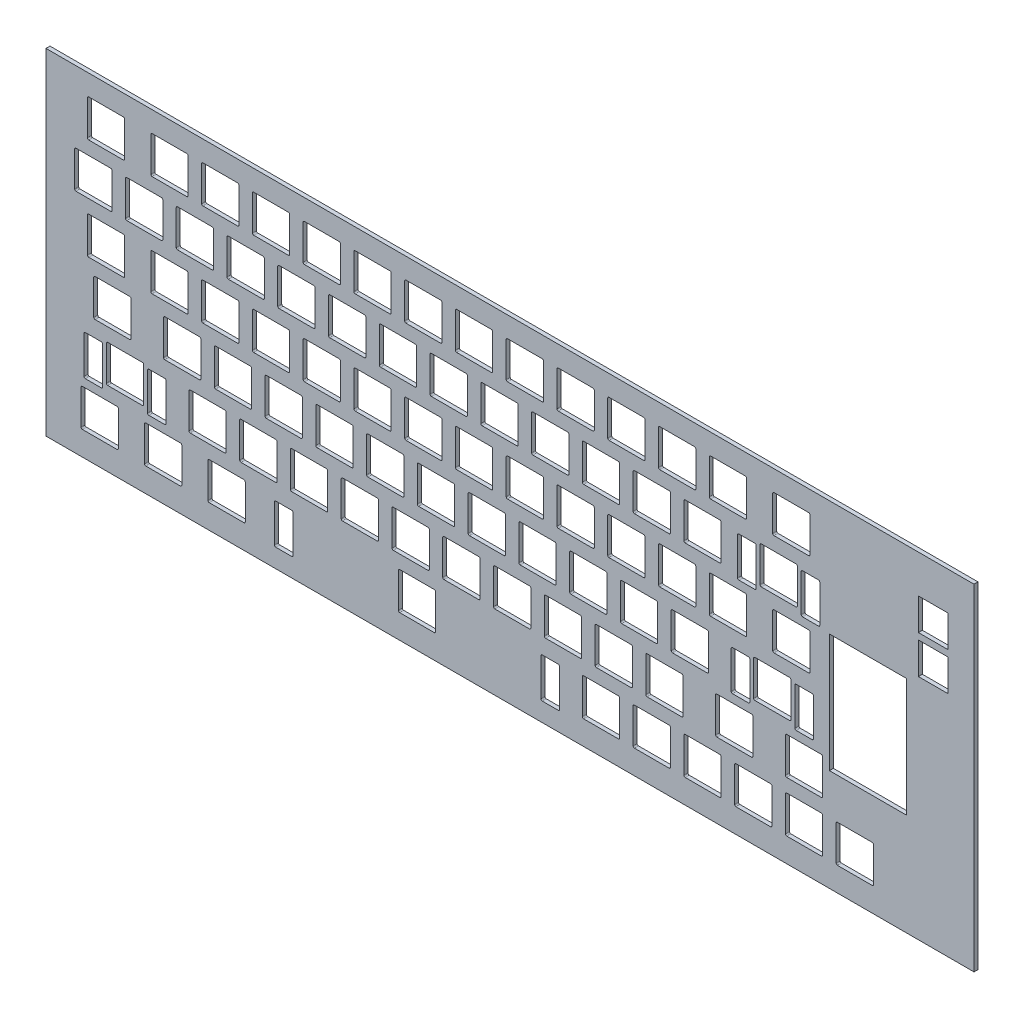
SolidWorks part; units mm, degrees
ref_plane "Front Plane" through (0, 0, 0) normal (0, 0, 1) x (1, 0, 0)
ref_plane "Top Plane" through (0, 0, 0) normal (0, 1, 0) x (1, 0, 0)
ref_plane "Right Plane" through (0, 0, 0) normal (1, 0, 0) x (0, 0, -1)
sketch "Sketch6" plane through (0, 0, 0) normal (0, 0, 1) x (1, 0, 0)
  line L0 (7.7875, -2.525) -> (20.7875, -2.525)
  line L1 (7.7875, -16.525) -> (20.7875, -16.525)
  line L2 (7.2875, -3.025) -> (7.2875, -16.025)
  line L3 (21.2875, -3.025) -> (21.2875, -16.025)
  line L4 (31.6, -2.525) -> (44.6, -2.525)
  line L5 (31.6, -16.525) -> (44.6, -16.525)
  line L6 (31.1, -3.025) -> (31.1, -16.025)
  line L7 (45.1, -3.025) -> (45.1, -16.025)
  line L8 (50.65, -2.525) -> (63.65, -2.525)
  line L9 (50.65, -16.525) -> (63.65, -16.525)
  line L10 (50.15, -3.025) -> (50.15, -16.025)
  line L11 (64.15, -3.025) -> (64.15, -16.025)
  line L12 (69.7, -2.525) -> (82.7, -2.525)
  line L13 (69.7, -16.525) -> (82.7, -16.525)
  line L14 (69.2, -3.025) -> (69.2, -16.025)
  line L15 (83.2, -3.025) -> (83.2, -16.025)
  line L16 (88.75, -2.525) -> (101.75, -2.525)
  line L17 (88.75, -16.525) -> (101.75, -16.525)
  line L18 (88.25, -3.025) -> (88.25, -16.025)
  line L19 (102.25, -3.025) -> (102.25, -16.025)
  line L20 (107.8, -2.525) -> (120.8, -2.525)
  line L21 (107.8, -16.525) -> (120.8, -16.525)
  line L22 (107.3, -3.025) -> (107.3, -16.025)
  line L23 (121.3, -3.025) -> (121.3, -16.025)
  line L24 (126.85, -2.525) -> (139.85, -2.525)
  line L25 (126.85, -16.525) -> (139.85, -16.525)
  line L26 (126.35, -3.025) -> (126.35, -16.025)
  line L27 (140.35, -3.025) -> (140.35, -16.025)
  line L28 (145.9, -2.525) -> (158.9, -2.525)
  line L29 (145.9, -16.525) -> (158.9, -16.525)
  line L30 (145.4, -3.025) -> (145.4, -16.025)
  line L31 (159.4, -3.025) -> (159.4, -16.025)
  line L32 (164.95, -2.525) -> (177.95, -2.525)
  line L33 (164.95, -16.525) -> (177.95, -16.525)
  line L34 (164.45, -3.025) -> (164.45, -16.025)
  line L35 (178.45, -3.025) -> (178.45, -16.025)
  line L36 (184, -2.525) -> (197, -2.525)
  line L37 (184, -16.525) -> (197, -16.525)
  line L38 (183.5, -3.025) -> (183.5, -16.025)
  line L39 (197.5, -3.025) -> (197.5, -16.025)
  line L40 (203.05, -2.525) -> (216.05, -2.525)
  line L41 (203.05, -16.525) -> (216.05, -16.525)
  line L42 (202.55, -3.025) -> (202.55, -16.025)
  line L43 (216.55, -3.025) -> (216.55, -16.025)
  line L44 (222.1, -2.525) -> (235.1, -2.525)
  line L45 (222.1, -16.525) -> (235.1, -16.525)
  line L46 (221.6, -3.025) -> (221.6, -16.025)
  line L47 (235.6, -3.025) -> (235.6, -16.025)
  line L48 (241.15, -2.525) -> (254.15, -2.525)
  line L49 (241.15, -16.525) -> (254.15, -16.525)
  line L50 (240.65, -3.025) -> (240.65, -16.025)
  line L51 (254.65, -3.025) -> (254.65, -16.025)
  line L52 (264.9625, -2.525) -> (277.9625, -2.525)
  line L53 (264.9625, -16.525) -> (277.9625, -16.525)
  line L54 (264.4625, -3.025) -> (264.4625, -16.025)
  line L55 (278.4625, -3.025) -> (278.4625, -16.025)
  line L56 (3.025, -21.575) -> (16.025, -21.575)
  line L57 (3.025, -35.575) -> (16.025, -35.575)
  line L58 (2.525, -22.075) -> (2.525, -35.075)
  line L59 (16.525, -22.075) -> (16.525, -35.075)
  line L60 (22.075, -21.575) -> (35.075, -21.575)
  line L61 (22.075, -35.575) -> (35.075, -35.575)
  line L62 (21.575, -22.075) -> (21.575, -35.075)
  line L63 (35.575, -22.075) -> (35.575, -35.075)
  line L64 (41.125, -21.575) -> (54.125, -21.575)
  line L65 (41.125, -35.575) -> (54.125, -35.575)
  line L66 (40.625, -22.075) -> (40.625, -35.075)
  line L67 (54.625, -22.075) -> (54.625, -35.075)
  line L68 (60.175, -21.575) -> (73.175, -21.575)
  line L69 (60.175, -35.575) -> (73.175, -35.575)
  line L70 (59.675, -22.075) -> (59.675, -35.075)
  line L71 (73.675, -22.075) -> (73.675, -35.075)
  line L72 (79.225, -21.575) -> (92.225, -21.575)
  line L73 (79.225, -35.575) -> (92.225, -35.575)
  line L74 (78.725, -22.075) -> (78.725, -35.075)
  line L75 (92.725, -22.075) -> (92.725, -35.075)
  line L76 (98.275, -21.575) -> (111.275, -21.575)
  line L77 (98.275, -35.575) -> (111.275, -35.575)
  line L78 (97.775, -22.075) -> (97.775, -35.075)
  line L79 (111.775, -22.075) -> (111.775, -35.075)
  line L80 (117.325, -21.575) -> (130.325, -21.575)
  line L81 (117.325, -35.575) -> (130.325, -35.575)
  line L82 (116.825, -22.075) -> (116.825, -35.075)
  line L83 (130.825, -22.075) -> (130.825, -35.075)
  line L84 (136.375, -21.575) -> (149.375, -21.575)
  line L85 (136.375, -35.575) -> (149.375, -35.575)
  line L86 (135.875, -22.075) -> (135.875, -35.075)
  line L87 (149.875, -22.075) -> (149.875, -35.075)
  line L88 (155.425, -21.575) -> (168.425, -21.575)
  line L89 (155.425, -35.575) -> (168.425, -35.575)
  line L90 (154.925, -22.075) -> (154.925, -35.075)
  line L91 (168.925, -22.075) -> (168.925, -35.075)
  line L92 (174.475, -21.575) -> (187.475, -21.575)
  line L93 (174.475, -35.575) -> (187.475, -35.575)
  line L94 (173.975, -22.075) -> (173.975, -35.075)
  line L95 (187.975, -22.075) -> (187.975, -35.075)
  line L96 (193.525, -21.575) -> (206.525, -21.575)
  line L97 (193.525, -35.575) -> (206.525, -35.575)
  line L98 (193.025, -22.075) -> (193.025, -35.075)
  line L99 (207.025, -22.075) -> (207.025, -35.075)
  line L100 (212.575, -21.575) -> (225.575, -21.575)
  line L101 (212.575, -35.575) -> (225.575, -35.575)
  line L102 (212.075, -22.075) -> (212.075, -35.075)
  line L103 (226.075, -22.075) -> (226.075, -35.075)
  line L104 (231.625, -21.575) -> (244.625, -21.575)
  line L105 (231.625, -35.575) -> (244.625, -35.575)
  line L106 (231.125, -22.075) -> (231.125, -35.075)
  line L107 (245.125, -22.075) -> (245.125, -35.075)
  line L108 (260.2, -21.575) -> (273.2, -21.575)
  line L109 (260.2, -35.575) -> (273.2, -35.575)
  line L110 (259.7, -22.075) -> (259.7, -35.075)
  line L111 (273.7, -22.075) -> (273.7, -35.075)
  line L112 (251.762, -22.575) -> (257.762, -22.575)
  line L113 (251.762, -37.575) -> (257.762, -37.575)
  line L114 (251.262, -23.075) -> (251.262, -37.075)
  line L115 (258.262, -23.075) -> (258.262, -37.075)
  line L116 (275.638, -22.575) -> (281.638, -22.575)
  line L117 (275.638, -37.575) -> (281.638, -37.575)
  line L118 (275.138, -23.075) -> (275.138, -37.075)
  line L119 (282.138, -23.075) -> (282.138, -37.075)
  line L120 (7.7875, -40.625) -> (20.7875, -40.625)
  line L121 (7.7875, -54.625) -> (20.7875, -54.625)
  line L122 (7.2875, -41.125) -> (7.2875, -54.125)
  line L123 (21.2875, -41.125) -> (21.2875, -54.125)
  line L124 (31.6, -40.625) -> (44.6, -40.625)
  line L125 (31.6, -54.625) -> (44.6, -54.625)
  line L126 (31.1, -41.125) -> (31.1, -54.125)
  line L127 (45.1, -41.125) -> (45.1, -54.125)
  line L128 (50.65, -40.625) -> (63.65, -40.625)
  line L129 (50.65, -54.625) -> (63.65, -54.625)
  line L130 (50.15, -41.125) -> (50.15, -54.125)
  line L131 (64.15, -41.125) -> (64.15, -54.125)
  line L132 (69.7, -40.625) -> (82.7, -40.625)
  line L133 (69.7, -54.625) -> (82.7, -54.625)
  line L134 (69.2, -41.125) -> (69.2, -54.125)
  line L135 (83.2, -41.125) -> (83.2, -54.125)
  line L136 (88.75, -40.625) -> (101.75, -40.625)
  line L137 (88.75, -54.625) -> (101.75, -54.625)
  line L138 (88.25, -41.125) -> (88.25, -54.125)
  line L139 (102.25, -41.125) -> (102.25, -54.125)
  line L140 (107.8, -40.625) -> (120.8, -40.625)
  line L141 (107.8, -54.625) -> (120.8, -54.625)
  line L142 (107.3, -41.125) -> (107.3, -54.125)
  line L143 (121.3, -41.125) -> (121.3, -54.125)
  line L144 (126.85, -40.625) -> (139.85, -40.625)
  line L145 (126.85, -54.625) -> (139.85, -54.625)
  line L146 (126.35, -41.125) -> (126.35, -54.125)
  line L147 (140.35, -41.125) -> (140.35, -54.125)
  line L148 (145.9, -40.625) -> (158.9, -40.625)
  line L149 (145.9, -54.625) -> (158.9, -54.625)
  line L150 (145.4, -41.125) -> (145.4, -54.125)
  line L151 (159.4, -41.125) -> (159.4, -54.125)
  line L152 (164.95, -40.625) -> (177.95, -40.625)
  line L153 (164.95, -54.625) -> (177.95, -54.625)
  line L154 (164.45, -41.125) -> (164.45, -54.125)
  line L155 (178.45, -41.125) -> (178.45, -54.125)
  line L156 (184, -40.625) -> (197, -40.625)
  line L157 (184, -54.625) -> (197, -54.625)
  line L158 (183.5, -41.125) -> (183.5, -54.125)
  line L159 (197.5, -41.125) -> (197.5, -54.125)
  line L160 (203.05, -40.625) -> (216.05, -40.625)
  line L161 (203.05, -54.625) -> (216.05, -54.625)
  line L162 (202.55, -41.125) -> (202.55, -54.125)
  line L163 (216.55, -41.125) -> (216.55, -54.125)
  line L164 (222.1, -40.625) -> (235.1, -40.625)
  line L165 (222.1, -54.625) -> (235.1, -54.625)
  line L166 (221.6, -41.125) -> (221.6, -54.125)
  line L167 (235.6, -41.125) -> (235.6, -54.125)
  line L168 (241.15, -40.625) -> (254.15, -40.625)
  line L169 (241.15, -54.625) -> (254.15, -54.625)
  line L170 (240.65, -41.125) -> (240.65, -54.125)
  line L171 (254.65, -41.125) -> (254.65, -54.125)
  line L172 (264.9625, -40.625) -> (277.9625, -40.625)
  line L173 (264.9625, -54.625) -> (277.9625, -54.625)
  line L174 (264.4625, -41.125) -> (264.4625, -54.125)
  line L175 (278.4625, -41.125) -> (278.4625, -54.125)
  line L176 (10.1687, -59.675) -> (23.1687, -59.675)
  line L177 (10.1687, -73.675) -> (23.1687, -73.675)
  line L178 (9.6688, -60.175) -> (9.6688, -73.175)
  line L179 (23.6687, -60.175) -> (23.6687, -73.175)
  line L180 (36.3625, -59.675) -> (49.3625, -59.675)
  line L181 (36.3625, -73.675) -> (49.3625, -73.675)
  line L182 (35.8625, -60.175) -> (35.8625, -73.175)
  line L183 (49.8625, -60.175) -> (49.8625, -73.175)
  line L184 (55.4125, -59.675) -> (68.4125, -59.675)
  line L185 (55.4125, -73.675) -> (68.4125, -73.675)
  line L186 (54.9125, -60.175) -> (54.9125, -73.175)
  line L187 (68.9125, -60.175) -> (68.9125, -73.175)
  line L188 (74.4625, -59.675) -> (87.4625, -59.675)
  line L189 (74.4625, -73.675) -> (87.4625, -73.675)
  line L190 (73.9625, -60.175) -> (73.9625, -73.175)
  line L191 (87.9625, -60.175) -> (87.9625, -73.175)
  line L192 (93.5125, -59.675) -> (106.5125, -59.675)
  line L193 (93.5125, -73.675) -> (106.5125, -73.675)
  line L194 (93.0125, -60.175) -> (93.0125, -73.175)
  line L195 (107.0125, -60.175) -> (107.0125, -73.175)
  line L196 (112.5625, -59.675) -> (125.5625, -59.675)
  line L197 (112.5625, -73.675) -> (125.5625, -73.675)
  line L198 (112.0625, -60.175) -> (112.0625, -73.175)
  line L199 (126.0625, -60.175) -> (126.0625, -73.175)
  line L200 (131.6125, -59.675) -> (144.6125, -59.675)
  line L201 (131.6125, -73.675) -> (144.6125, -73.675)
  line L202 (131.1125, -60.175) -> (131.1125, -73.175)
  line L203 (145.1125, -60.175) -> (145.1125, -73.175)
  line L204 (150.6625, -59.675) -> (163.6625, -59.675)
  line L205 (150.6625, -73.675) -> (163.6625, -73.675)
  line L206 (150.1625, -60.175) -> (150.1625, -73.175)
  line L207 (164.1625, -60.175) -> (164.1625, -73.175)
  line L208 (169.7125, -59.675) -> (182.7125, -59.675)
  line L209 (169.7125, -73.675) -> (182.7125, -73.675)
  line L210 (169.2125, -60.175) -> (169.2125, -73.175)
  line L211 (183.2125, -60.175) -> (183.2125, -73.175)
  line L212 (188.7625, -59.675) -> (201.7625, -59.675)
  line L213 (188.7625, -73.675) -> (201.7625, -73.675)
  line L214 (188.2625, -60.175) -> (188.2625, -73.175)
  line L215 (202.2625, -60.175) -> (202.2625, -73.175)
  line L216 (207.8125, -59.675) -> (220.8125, -59.675)
  line L217 (207.8125, -73.675) -> (220.8125, -73.675)
  line L218 (207.3125, -60.175) -> (207.3125, -73.175)
  line L219 (221.3125, -60.175) -> (221.3125, -73.175)
  line L220 (226.8625, -59.675) -> (239.8625, -59.675)
  line L221 (226.8625, -73.675) -> (239.8625, -73.675)
  line L222 (226.3625, -60.175) -> (226.3625, -73.175)
  line L223 (240.3625, -60.175) -> (240.3625, -73.175)
  line L224 (257.8188, -59.675) -> (270.8188, -59.675)
  line L225 (257.8188, -73.675) -> (270.8188, -73.675)
  line L226 (257.3188, -60.175) -> (257.3188, -73.175)
  line L227 (271.3188, -60.175) -> (271.3188, -73.175)
  line L228 (249.3808, -60.675) -> (255.3807, -60.675)
  line L229 (249.3808, -75.675) -> (255.3807, -75.675)
  line L230 (248.8808, -61.175) -> (248.8808, -75.175)
  line L231 (255.8807, -61.175) -> (255.8807, -75.175)
  line L232 (273.2568, -60.675) -> (279.2568, -60.675)
  line L233 (273.2568, -75.675) -> (279.2568, -75.675)
  line L234 (272.7568, -61.175) -> (272.7568, -75.175)
  line L235 (279.7568, -61.175) -> (279.7568, -75.175)
  line L236 (14.9313, -78.725) -> (27.9312, -78.725)
  line L237 (14.9313, -92.725) -> (27.9312, -92.725)
  line L238 (14.4313, -79.225) -> (14.4313, -92.225)
  line L239 (28.4312, -79.225) -> (28.4312, -92.225)
  line L240 (6.4932, -79.725) -> (12.4932, -79.725)
  line L241 (6.4932, -94.725) -> (12.4932, -94.725)
  line L242 (5.9932, -80.225) -> (5.9932, -94.225)
  line L243 (12.9932, -80.225) -> (12.9932, -94.225)
  line L244 (30.3693, -79.725) -> (36.3693, -79.725)
  line L245 (30.3693, -94.725) -> (36.3693, -94.725)
  line L246 (29.8693, -80.225) -> (29.8693, -94.225)
  line L247 (36.8693, -80.225) -> (36.8693, -94.225)
  line L248 (45.8875, -78.725) -> (58.8875, -78.725)
  line L249 (45.8875, -92.725) -> (58.8875, -92.725)
  line L250 (45.3875, -79.225) -> (45.3875, -92.225)
  line L251 (59.3875, -79.225) -> (59.3875, -92.225)
  line L252 (64.9375, -78.725) -> (77.9375, -78.725)
  line L253 (64.9375, -92.725) -> (77.9375, -92.725)
  line L254 (64.4375, -79.225) -> (64.4375, -92.225)
  line L255 (78.4375, -79.225) -> (78.4375, -92.225)
  line L256 (83.9875, -78.725) -> (96.9875, -78.725)
  line L257 (83.9875, -92.725) -> (96.9875, -92.725)
  line L258 (83.4875, -79.225) -> (83.4875, -92.225)
  line L259 (97.4875, -79.225) -> (97.4875, -92.225)
  line L260 (103.0375, -78.725) -> (116.0375, -78.725)
  line L261 (103.0375, -92.725) -> (116.0375, -92.725)
  line L262 (102.5375, -79.225) -> (102.5375, -92.225)
  line L263 (116.5375, -79.225) -> (116.5375, -92.225)
  line L264 (122.0875, -78.725) -> (135.0875, -78.725)
  line L265 (122.0875, -92.725) -> (135.0875, -92.725)
  line L266 (121.5875, -79.225) -> (121.5875, -92.225)
  line L267 (135.5875, -79.225) -> (135.5875, -92.225)
  line L268 (141.1375, -78.725) -> (154.1375, -78.725)
  line L269 (141.1375, -92.725) -> (154.1375, -92.725)
  line L270 (140.6375, -79.225) -> (140.6375, -92.225)
  line L271 (154.6375, -79.225) -> (154.6375, -92.225)
  line L272 (160.1875, -78.725) -> (173.1875, -78.725)
  line L273 (160.1875, -92.725) -> (173.1875, -92.725)
  line L274 (159.6875, -79.225) -> (159.6875, -92.225)
  line L275 (173.6875, -79.225) -> (173.6875, -92.225)
  line L276 (179.2375, -78.725) -> (192.2375, -78.725)
  line L277 (179.2375, -92.725) -> (192.2375, -92.725)
  line L278 (178.7375, -79.225) -> (178.7375, -92.225)
  line L279 (192.7375, -79.225) -> (192.7375, -92.225)
  line L280 (198.2875, -78.725) -> (211.2875, -78.725)
  line L281 (198.2875, -92.725) -> (211.2875, -92.725)
  line L282 (197.7875, -79.225) -> (197.7875, -92.225)
  line L283 (211.7875, -79.225) -> (211.7875, -92.225)
  line L284 (217.3375, -78.725) -> (230.3375, -78.725)
  line L285 (217.3375, -92.725) -> (230.3375, -92.725)
  line L286 (216.8375, -79.225) -> (216.8375, -92.225)
  line L287 (230.8375, -79.225) -> (230.8375, -92.225)
  line L288 (243.5312, -78.725) -> (256.5312, -78.725)
  line L289 (243.5312, -92.725) -> (256.5312, -92.725)
  line L290 (243.0312, -79.225) -> (243.0312, -92.225)
  line L291 (257.0312, -79.225) -> (257.0312, -92.225)
  line L292 (269.725, -78.725) -> (282.725, -78.725)
  line L293 (269.725, -92.725) -> (282.725, -92.725)
  line L294 (269.225, -79.225) -> (269.225, -92.225)
  line L295 (283.225, -79.225) -> (283.225, -92.225)
  line L296 (5.4063, -97.775) -> (18.4062, -97.775)
  line L297 (5.4063, -111.775) -> (18.4062, -111.775)
  line L298 (4.9062, -98.275) -> (4.9062, -111.275)
  line L299 (18.9062, -98.275) -> (18.9062, -111.275)
  line L300 (29.2188, -97.775) -> (42.2188, -97.775)
  line L301 (29.2188, -111.775) -> (42.2188, -111.775)
  line L302 (28.7188, -98.275) -> (28.7188, -111.275)
  line L303 (42.7188, -98.275) -> (42.7188, -111.275)
  line L304 (53.0312, -97.775) -> (66.0312, -97.775)
  line L305 (53.0312, -111.775) -> (66.0312, -111.775)
  line L306 (52.5312, -98.275) -> (52.5312, -111.275)
  line L307 (66.5312, -98.275) -> (66.5312, -111.275)
  line L308 (124.4688, -97.775) -> (137.4688, -97.775)
  line L309 (124.4688, -111.775) -> (137.4688, -111.775)
  line L310 (123.9688, -98.275) -> (123.9688, -111.275)
  line L311 (137.9688, -98.275) -> (137.9688, -111.275)
  line L312 (77.9688, -98.775) -> (83.9688, -98.775)
  line L313 (77.9688, -113.775) -> (83.9688, -113.775)
  line L314 (77.4688, -99.275) -> (77.4688, -113.275)
  line L315 (84.4688, -99.275) -> (84.4688, -113.275)
  line L316 (177.9688, -98.775) -> (183.9688, -98.775)
  line L317 (177.9688, -113.775) -> (183.9688, -113.775)
  line L318 (177.4688, -99.275) -> (177.4688, -113.275)
  line L319 (184.4688, -99.275) -> (184.4688, -113.275)
  line L320 (193.525, -97.775) -> (206.525, -97.775)
  line L321 (193.525, -111.775) -> (206.525, -111.775)
  line L322 (193.025, -98.275) -> (193.025, -111.275)
  line L323 (207.025, -98.275) -> (207.025, -111.275)
  line L324 (212.575, -97.775) -> (225.575, -97.775)
  line L325 (212.575, -111.775) -> (225.575, -111.775)
  line L326 (212.075, -98.275) -> (212.075, -111.275)
  line L327 (226.075, -98.275) -> (226.075, -111.275)
  line L328 (231.625, -97.775) -> (244.625, -97.775)
  line L329 (231.625, -111.775) -> (244.625, -111.775)
  line L330 (231.125, -98.275) -> (231.125, -111.275)
  line L331 (245.125, -98.275) -> (245.125, -111.275)
  line L332 (250.675, -97.775) -> (263.675, -97.775)
  line L333 (250.675, -111.775) -> (263.675, -111.775)
  line L334 (250.175, -98.275) -> (250.175, -111.275)
  line L335 (264.175, -98.275) -> (264.175, -111.275)
  line L336 (269.725, -97.775) -> (282.725, -97.775)
  line L337 (269.725, -111.775) -> (282.725, -111.775)
  line L338 (269.225, -98.275) -> (269.225, -111.275)
  line L339 (283.225, -98.275) -> (283.225, -111.275)
  line L340 (288.775, -97.775) -> (301.775, -97.775)
  line L341 (288.775, -111.775) -> (301.775, -111.775)
  line L342 (288.275, -98.275) -> (288.275, -111.275)
  line L343 (302.275, -98.275) -> (302.275, -111.275)
  line L346 (0, -114.3) -> (0, 0)
  line L348 (0, 0) -> (340, 0)
  line L350 (0, -114.3) -> (340, -114.3)
  line L351 (340, 0) -> (340, -114.3)
  line L352 (285.74, -38.08) -> (314.74, -38.08)
  line L353 (285.74, -38.08) -> (285.74, -82.5)
  line L354 (285.74, -82.5) -> (314.74, -82.5)
  line L355 (314.74, -38.08) -> (314.74, -82.5)
  line L356 (319.14, -9.03) -> (330.19, -9.03)
  line L357 (319.14, -9.03) -> (319.14, -20.93)
  line L358 (319.14, -20.93) -> (330.19, -20.93)
  line L359 (330.19, -9.03) -> (330.19, -20.93)
  line L360 (319.14, -23.33) -> (330.19, -23.33)
  line L361 (319.14, -23.33) -> (319.14, -35.23)
  line L362 (319.14, -35.23) -> (330.19, -35.23)
  line L363 (330.19, -23.33) -> (330.19, -35.23)
  arc A0 (7.7875, -2.525) -> (7.2875, -3.025) centre (7.7875, -3.025) ccw
  arc A1 (21.2875, -3.025) -> (20.7875, -2.525) centre (20.7875, -3.025) ccw
  arc A2 (7.2875, -16.025) -> (7.7875, -16.525) centre (7.7875, -16.025) ccw
  arc A3 (20.7875, -16.525) -> (21.2875, -16.025) centre (20.7875, -16.025) ccw
  arc A4 (31.6, -2.525) -> (31.1, -3.025) centre (31.6, -3.025) ccw
  arc A5 (45.1, -3.025) -> (44.6, -2.525) centre (44.6, -3.025) ccw
  arc A6 (31.1, -16.025) -> (31.6, -16.525) centre (31.6, -16.025) ccw
  arc A7 (44.6, -16.525) -> (45.1, -16.025) centre (44.6, -16.025) ccw
  arc A8 (50.65, -2.525) -> (50.15, -3.025) centre (50.65, -3.025) ccw
  arc A9 (64.15, -3.025) -> (63.65, -2.525) centre (63.65, -3.025) ccw
  arc A10 (50.15, -16.025) -> (50.65, -16.525) centre (50.65, -16.025) ccw
  arc A11 (63.65, -16.525) -> (64.15, -16.025) centre (63.65, -16.025) ccw
  arc A12 (69.7, -2.525) -> (69.2, -3.025) centre (69.7, -3.025) ccw
  arc A13 (83.2, -3.025) -> (82.7, -2.525) centre (82.7, -3.025) ccw
  arc A14 (69.2, -16.025) -> (69.7, -16.525) centre (69.7, -16.025) ccw
  arc A15 (82.7, -16.525) -> (83.2, -16.025) centre (82.7, -16.025) ccw
  arc A16 (88.75, -2.525) -> (88.25, -3.025) centre (88.75, -3.025) ccw
  arc A17 (102.25, -3.025) -> (101.75, -2.525) centre (101.75, -3.025) ccw
  arc A18 (88.25, -16.025) -> (88.75, -16.525) centre (88.75, -16.025) ccw
  arc A19 (101.75, -16.525) -> (102.25, -16.025) centre (101.75, -16.025) ccw
  arc A20 (107.8, -2.525) -> (107.3, -3.025) centre (107.8, -3.025) ccw
  arc A21 (121.3, -3.025) -> (120.8, -2.525) centre (120.8, -3.025) ccw
  arc A22 (107.3, -16.025) -> (107.8, -16.525) centre (107.8, -16.025) ccw
  arc A23 (120.8, -16.525) -> (121.3, -16.025) centre (120.8, -16.025) ccw
  arc A24 (126.85, -2.525) -> (126.35, -3.025) centre (126.85, -3.025) ccw
  arc A25 (140.35, -3.025) -> (139.85, -2.525) centre (139.85, -3.025) ccw
  arc A26 (126.35, -16.025) -> (126.85, -16.525) centre (126.85, -16.025) ccw
  arc A27 (139.85, -16.525) -> (140.35, -16.025) centre (139.85, -16.025) ccw
  arc A28 (145.9, -2.525) -> (145.4, -3.025) centre (145.9, -3.025) ccw
  arc A29 (159.4, -3.025) -> (158.9, -2.525) centre (158.9, -3.025) ccw
  arc A30 (145.4, -16.025) -> (145.9, -16.525) centre (145.9, -16.025) ccw
  arc A31 (158.9, -16.525) -> (159.4, -16.025) centre (158.9, -16.025) ccw
  arc A32 (164.95, -2.525) -> (164.45, -3.025) centre (164.95, -3.025) ccw
  arc A33 (178.45, -3.025) -> (177.95, -2.525) centre (177.95, -3.025) ccw
  arc A34 (164.45, -16.025) -> (164.95, -16.525) centre (164.95, -16.025) ccw
  arc A35 (177.95, -16.525) -> (178.45, -16.025) centre (177.95, -16.025) ccw
  arc A36 (184, -2.525) -> (183.5, -3.025) centre (184, -3.025) ccw
  arc A37 (197.5, -3.025) -> (197, -2.525) centre (197, -3.025) ccw
  arc A38 (183.5, -16.025) -> (184, -16.525) centre (184, -16.025) ccw
  arc A39 (197, -16.525) -> (197.5, -16.025) centre (197, -16.025) ccw
  arc A40 (203.05, -2.525) -> (202.55, -3.025) centre (203.05, -3.025) ccw
  arc A41 (216.55, -3.025) -> (216.05, -2.525) centre (216.05, -3.025) ccw
  arc A42 (202.55, -16.025) -> (203.05, -16.525) centre (203.05, -16.025) ccw
  arc A43 (216.05, -16.525) -> (216.55, -16.025) centre (216.05, -16.025) ccw
  arc A44 (222.1, -2.525) -> (221.6, -3.025) centre (222.1, -3.025) ccw
  arc A45 (235.6, -3.025) -> (235.1, -2.525) centre (235.1, -3.025) ccw
  arc A46 (221.6, -16.025) -> (222.1, -16.525) centre (222.1, -16.025) ccw
  arc A47 (235.1, -16.525) -> (235.6, -16.025) centre (235.1, -16.025) ccw
  arc A48 (241.15, -2.525) -> (240.65, -3.025) centre (241.15, -3.025) ccw
  arc A49 (254.65, -3.025) -> (254.15, -2.525) centre (254.15, -3.025) ccw
  arc A50 (240.65, -16.025) -> (241.15, -16.525) centre (241.15, -16.025) ccw
  arc A51 (254.15, -16.525) -> (254.65, -16.025) centre (254.15, -16.025) ccw
  arc A52 (264.9625, -2.525) -> (264.4625, -3.025) centre (264.9625, -3.025) ccw
  arc A53 (278.4625, -3.025) -> (277.9625, -2.525) centre (277.9625, -3.025) ccw
  arc A54 (264.4625, -16.025) -> (264.9625, -16.525) centre (264.9625, -16.025) ccw
  arc A55 (277.9625, -16.525) -> (278.4625, -16.025) centre (277.9625, -16.025) ccw
  arc A56 (3.025, -21.575) -> (2.525, -22.075) centre (3.025, -22.075) ccw
  arc A57 (16.525, -22.075) -> (16.025, -21.575) centre (16.025, -22.075) ccw
  arc A58 (2.525, -35.075) -> (3.025, -35.575) centre (3.025, -35.075) ccw
  arc A59 (16.025, -35.575) -> (16.525, -35.075) centre (16.025, -35.075) ccw
  arc A60 (22.075, -21.575) -> (21.575, -22.075) centre (22.075, -22.075) ccw
  arc A61 (35.575, -22.075) -> (35.075, -21.575) centre (35.075, -22.075) ccw
  arc A62 (21.575, -35.075) -> (22.075, -35.575) centre (22.075, -35.075) ccw
  arc A63 (35.075, -35.575) -> (35.575, -35.075) centre (35.075, -35.075) ccw
  arc A64 (41.125, -21.575) -> (40.625, -22.075) centre (41.125, -22.075) ccw
  arc A65 (54.625, -22.075) -> (54.125, -21.575) centre (54.125, -22.075) ccw
  arc A66 (40.625, -35.075) -> (41.125, -35.575) centre (41.125, -35.075) ccw
  arc A67 (54.125, -35.575) -> (54.625, -35.075) centre (54.125, -35.075) ccw
  arc A68 (60.175, -21.575) -> (59.675, -22.075) centre (60.175, -22.075) ccw
  arc A69 (73.675, -22.075) -> (73.175, -21.575) centre (73.175, -22.075) ccw
  arc A70 (59.675, -35.075) -> (60.175, -35.575) centre (60.175, -35.075) ccw
  arc A71 (73.175, -35.575) -> (73.675, -35.075) centre (73.175, -35.075) ccw
  arc A72 (79.225, -21.575) -> (78.725, -22.075) centre (79.225, -22.075) ccw
  arc A73 (92.725, -22.075) -> (92.225, -21.575) centre (92.225, -22.075) ccw
  arc A74 (78.725, -35.075) -> (79.225, -35.575) centre (79.225, -35.075) ccw
  arc A75 (92.225, -35.575) -> (92.725, -35.075) centre (92.225, -35.075) ccw
  arc A76 (98.275, -21.575) -> (97.775, -22.075) centre (98.275, -22.075) ccw
  arc A77 (111.775, -22.075) -> (111.275, -21.575) centre (111.275, -22.075) ccw
  arc A78 (97.775, -35.075) -> (98.275, -35.575) centre (98.275, -35.075) ccw
  arc A79 (111.275, -35.575) -> (111.775, -35.075) centre (111.275, -35.075) ccw
  arc A80 (117.325, -21.575) -> (116.825, -22.075) centre (117.325, -22.075) ccw
  arc A81 (130.825, -22.075) -> (130.325, -21.575) centre (130.325, -22.075) ccw
  arc A82 (116.825, -35.075) -> (117.325, -35.575) centre (117.325, -35.075) ccw
  arc A83 (130.325, -35.575) -> (130.825, -35.075) centre (130.325, -35.075) ccw
  arc A84 (136.375, -21.575) -> (135.875, -22.075) centre (136.375, -22.075) ccw
  arc A85 (149.875, -22.075) -> (149.375, -21.575) centre (149.375, -22.075) ccw
  arc A86 (135.875, -35.075) -> (136.375, -35.575) centre (136.375, -35.075) ccw
  arc A87 (149.375, -35.575) -> (149.875, -35.075) centre (149.375, -35.075) ccw
  arc A88 (155.425, -21.575) -> (154.925, -22.075) centre (155.425, -22.075) ccw
  arc A89 (168.925, -22.075) -> (168.425, -21.575) centre (168.425, -22.075) ccw
  arc A90 (154.925, -35.075) -> (155.425, -35.575) centre (155.425, -35.075) ccw
  arc A91 (168.425, -35.575) -> (168.925, -35.075) centre (168.425, -35.075) ccw
  arc A92 (174.475, -21.575) -> (173.975, -22.075) centre (174.475, -22.075) ccw
  arc A93 (187.975, -22.075) -> (187.475, -21.575) centre (187.475, -22.075) ccw
  arc A94 (173.975, -35.075) -> (174.475, -35.575) centre (174.475, -35.075) ccw
  arc A95 (187.475, -35.575) -> (187.975, -35.075) centre (187.475, -35.075) ccw
  arc A96 (193.525, -21.575) -> (193.025, -22.075) centre (193.525, -22.075) ccw
  arc A97 (207.025, -22.075) -> (206.525, -21.575) centre (206.525, -22.075) ccw
  arc A98 (193.025, -35.075) -> (193.525, -35.575) centre (193.525, -35.075) ccw
  arc A99 (206.525, -35.575) -> (207.025, -35.075) centre (206.525, -35.075) ccw
  arc A100 (212.575, -21.575) -> (212.075, -22.075) centre (212.575, -22.075) ccw
  arc A101 (226.075, -22.075) -> (225.575, -21.575) centre (225.575, -22.075) ccw
  arc A102 (212.075, -35.075) -> (212.575, -35.575) centre (212.575, -35.075) ccw
  arc A103 (225.575, -35.575) -> (226.075, -35.075) centre (225.575, -35.075) ccw
  arc A104 (231.625, -21.575) -> (231.125, -22.075) centre (231.625, -22.075) ccw
  arc A105 (245.125, -22.075) -> (244.625, -21.575) centre (244.625, -22.075) ccw
  arc A106 (231.125, -35.075) -> (231.625, -35.575) centre (231.625, -35.075) ccw
  arc A107 (244.625, -35.575) -> (245.125, -35.075) centre (244.625, -35.075) ccw
  arc A108 (260.2, -21.575) -> (259.7, -22.075) centre (260.2, -22.075) ccw
  arc A109 (273.7, -22.075) -> (273.2, -21.575) centre (273.2, -22.075) ccw
  arc A110 (259.7, -35.075) -> (260.2, -35.575) centre (260.2, -35.075) ccw
  arc A111 (273.2, -35.575) -> (273.7, -35.075) centre (273.2, -35.075) ccw
  arc A112 (251.762, -22.575) -> (251.262, -23.075) centre (251.762, -23.075) ccw
  arc A113 (258.262, -23.075) -> (257.762, -22.575) centre (257.762, -23.075) ccw
  arc A114 (251.262, -37.075) -> (251.762, -37.575) centre (251.762, -37.075) ccw
  arc A115 (257.762, -37.575) -> (258.262, -37.075) centre (257.762, -37.075) ccw
  arc A116 (275.638, -22.575) -> (275.138, -23.075) centre (275.638, -23.075) ccw
  arc A117 (282.138, -23.075) -> (281.638, -22.575) centre (281.638, -23.075) ccw
  arc A118 (275.138, -37.075) -> (275.638, -37.575) centre (275.638, -37.075) ccw
  arc A119 (281.638, -37.575) -> (282.138, -37.075) centre (281.638, -37.075) ccw
  arc A120 (7.7875, -40.625) -> (7.2875, -41.125) centre (7.7875, -41.125) ccw
  arc A121 (21.2875, -41.125) -> (20.7875, -40.625) centre (20.7875, -41.125) ccw
  arc A122 (7.2875, -54.125) -> (7.7875, -54.625) centre (7.7875, -54.125) ccw
  arc A123 (20.7875, -54.625) -> (21.2875, -54.125) centre (20.7875, -54.125) ccw
  arc A124 (31.6, -40.625) -> (31.1, -41.125) centre (31.6, -41.125) ccw
  arc A125 (45.1, -41.125) -> (44.6, -40.625) centre (44.6, -41.125) ccw
  arc A126 (31.1, -54.125) -> (31.6, -54.625) centre (31.6, -54.125) ccw
  arc A127 (44.6, -54.625) -> (45.1, -54.125) centre (44.6, -54.125) ccw
  arc A128 (50.65, -40.625) -> (50.15, -41.125) centre (50.65, -41.125) ccw
  arc A129 (64.15, -41.125) -> (63.65, -40.625) centre (63.65, -41.125) ccw
  arc A130 (50.15, -54.125) -> (50.65, -54.625) centre (50.65, -54.125) ccw
  arc A131 (63.65, -54.625) -> (64.15, -54.125) centre (63.65, -54.125) ccw
  arc A132 (69.7, -40.625) -> (69.2, -41.125) centre (69.7, -41.125) ccw
  arc A133 (83.2, -41.125) -> (82.7, -40.625) centre (82.7, -41.125) ccw
  arc A134 (69.2, -54.125) -> (69.7, -54.625) centre (69.7, -54.125) ccw
  arc A135 (82.7, -54.625) -> (83.2, -54.125) centre (82.7, -54.125) ccw
  arc A136 (88.75, -40.625) -> (88.25, -41.125) centre (88.75, -41.125) ccw
  arc A137 (102.25, -41.125) -> (101.75, -40.625) centre (101.75, -41.125) ccw
  arc A138 (88.25, -54.125) -> (88.75, -54.625) centre (88.75, -54.125) ccw
  arc A139 (101.75, -54.625) -> (102.25, -54.125) centre (101.75, -54.125) ccw
  arc A140 (107.8, -40.625) -> (107.3, -41.125) centre (107.8, -41.125) ccw
  arc A141 (121.3, -41.125) -> (120.8, -40.625) centre (120.8, -41.125) ccw
  arc A142 (107.3, -54.125) -> (107.8, -54.625) centre (107.8, -54.125) ccw
  arc A143 (120.8, -54.625) -> (121.3, -54.125) centre (120.8, -54.125) ccw
  arc A144 (126.85, -40.625) -> (126.35, -41.125) centre (126.85, -41.125) ccw
  arc A145 (140.35, -41.125) -> (139.85, -40.625) centre (139.85, -41.125) ccw
  arc A146 (126.35, -54.125) -> (126.85, -54.625) centre (126.85, -54.125) ccw
  arc A147 (139.85, -54.625) -> (140.35, -54.125) centre (139.85, -54.125) ccw
  arc A148 (145.9, -40.625) -> (145.4, -41.125) centre (145.9, -41.125) ccw
  arc A149 (159.4, -41.125) -> (158.9, -40.625) centre (158.9, -41.125) ccw
  arc A150 (145.4, -54.125) -> (145.9, -54.625) centre (145.9, -54.125) ccw
  arc A151 (158.9, -54.625) -> (159.4, -54.125) centre (158.9, -54.125) ccw
  arc A152 (164.95, -40.625) -> (164.45, -41.125) centre (164.95, -41.125) ccw
  arc A153 (178.45, -41.125) -> (177.95, -40.625) centre (177.95, -41.125) ccw
  arc A154 (164.45, -54.125) -> (164.95, -54.625) centre (164.95, -54.125) ccw
  arc A155 (177.95, -54.625) -> (178.45, -54.125) centre (177.95, -54.125) ccw
  arc A156 (184, -40.625) -> (183.5, -41.125) centre (184, -41.125) ccw
  arc A157 (197.5, -41.125) -> (197, -40.625) centre (197, -41.125) ccw
  arc A158 (183.5, -54.125) -> (184, -54.625) centre (184, -54.125) ccw
  arc A159 (197, -54.625) -> (197.5, -54.125) centre (197, -54.125) ccw
  arc A160 (203.05, -40.625) -> (202.55, -41.125) centre (203.05, -41.125) ccw
  arc A161 (216.55, -41.125) -> (216.05, -40.625) centre (216.05, -41.125) ccw
  arc A162 (202.55, -54.125) -> (203.05, -54.625) centre (203.05, -54.125) ccw
  arc A163 (216.05, -54.625) -> (216.55, -54.125) centre (216.05, -54.125) ccw
  arc A164 (222.1, -40.625) -> (221.6, -41.125) centre (222.1, -41.125) ccw
  arc A165 (235.6, -41.125) -> (235.1, -40.625) centre (235.1, -41.125) ccw
  arc A166 (221.6, -54.125) -> (222.1, -54.625) centre (222.1, -54.125) ccw
  arc A167 (235.1, -54.625) -> (235.6, -54.125) centre (235.1, -54.125) ccw
  arc A168 (241.15, -40.625) -> (240.65, -41.125) centre (241.15, -41.125) ccw
  arc A169 (254.65, -41.125) -> (254.15, -40.625) centre (254.15, -41.125) ccw
  arc A170 (240.65, -54.125) -> (241.15, -54.625) centre (241.15, -54.125) ccw
  arc A171 (254.15, -54.625) -> (254.65, -54.125) centre (254.15, -54.125) ccw
  arc A172 (264.9625, -40.625) -> (264.4625, -41.125) centre (264.9625, -41.125) ccw
  arc A173 (278.4625, -41.125) -> (277.9625, -40.625) centre (277.9625, -41.125) ccw
  arc A174 (264.4625, -54.125) -> (264.9625, -54.625) centre (264.9625, -54.125) ccw
  arc A175 (277.9625, -54.625) -> (278.4625, -54.125) centre (277.9625, -54.125) ccw
  arc A176 (10.1687, -59.675) -> (9.6688, -60.175) centre (10.1687, -60.175) ccw
  arc A177 (23.6687, -60.175) -> (23.1687, -59.675) centre (23.1687, -60.175) ccw
  arc A178 (9.6688, -73.175) -> (10.1687, -73.675) centre (10.1687, -73.175) ccw
  arc A179 (23.1687, -73.675) -> (23.6687, -73.175) centre (23.1687, -73.175) ccw
  arc A180 (36.3625, -59.675) -> (35.8625, -60.175) centre (36.3625, -60.175) ccw
  arc A181 (49.8625, -60.175) -> (49.3625, -59.675) centre (49.3625, -60.175) ccw
  arc A182 (35.8625, -73.175) -> (36.3625, -73.675) centre (36.3625, -73.175) ccw
  arc A183 (49.3625, -73.675) -> (49.8625, -73.175) centre (49.3625, -73.175) ccw
  arc A184 (55.4125, -59.675) -> (54.9125, -60.175) centre (55.4125, -60.175) ccw
  arc A185 (68.9125, -60.175) -> (68.4125, -59.675) centre (68.4125, -60.175) ccw
  arc A186 (54.9125, -73.175) -> (55.4125, -73.675) centre (55.4125, -73.175) ccw
  arc A187 (68.4125, -73.675) -> (68.9125, -73.175) centre (68.4125, -73.175) ccw
  arc A188 (74.4625, -59.675) -> (73.9625, -60.175) centre (74.4625, -60.175) ccw
  arc A189 (87.9625, -60.175) -> (87.4625, -59.675) centre (87.4625, -60.175) ccw
  arc A190 (73.9625, -73.175) -> (74.4625, -73.675) centre (74.4625, -73.175) ccw
  arc A191 (87.4625, -73.675) -> (87.9625, -73.175) centre (87.4625, -73.175) ccw
  arc A192 (93.5125, -59.675) -> (93.0125, -60.175) centre (93.5125, -60.175) ccw
  arc A193 (107.0125, -60.175) -> (106.5125, -59.675) centre (106.5125, -60.175) ccw
  arc A194 (93.0125, -73.175) -> (93.5125, -73.675) centre (93.5125, -73.175) ccw
  arc A195 (106.5125, -73.675) -> (107.0125, -73.175) centre (106.5125, -73.175) ccw
  arc A196 (112.5625, -59.675) -> (112.0625, -60.175) centre (112.5625, -60.175) ccw
  arc A197 (126.0625, -60.175) -> (125.5625, -59.675) centre (125.5625, -60.175) ccw
  arc A198 (112.0625, -73.175) -> (112.5625, -73.675) centre (112.5625, -73.175) ccw
  arc A199 (125.5625, -73.675) -> (126.0625, -73.175) centre (125.5625, -73.175) ccw
  arc A200 (131.6125, -59.675) -> (131.1125, -60.175) centre (131.6125, -60.175) ccw
  arc A201 (145.1125, -60.175) -> (144.6125, -59.675) centre (144.6125, -60.175) ccw
  arc A202 (131.1125, -73.175) -> (131.6125, -73.675) centre (131.6125, -73.175) ccw
  arc A203 (144.6125, -73.675) -> (145.1125, -73.175) centre (144.6125, -73.175) ccw
  arc A204 (150.6625, -59.675) -> (150.1625, -60.175) centre (150.6625, -60.175) ccw
  arc A205 (164.1625, -60.175) -> (163.6625, -59.675) centre (163.6625, -60.175) ccw
  arc A206 (150.1625, -73.175) -> (150.6625, -73.675) centre (150.6625, -73.175) ccw
  arc A207 (163.6625, -73.675) -> (164.1625, -73.175) centre (163.6625, -73.175) ccw
  arc A208 (169.7125, -59.675) -> (169.2125, -60.175) centre (169.7125, -60.175) ccw
  arc A209 (183.2125, -60.175) -> (182.7125, -59.675) centre (182.7125, -60.175) ccw
  arc A210 (169.2125, -73.175) -> (169.7125, -73.675) centre (169.7125, -73.175) ccw
  arc A211 (182.7125, -73.675) -> (183.2125, -73.175) centre (182.7125, -73.175) ccw
  arc A212 (188.7625, -59.675) -> (188.2625, -60.175) centre (188.7625, -60.175) ccw
  arc A213 (202.2625, -60.175) -> (201.7625, -59.675) centre (201.7625, -60.175) ccw
  arc A214 (188.2625, -73.175) -> (188.7625, -73.675) centre (188.7625, -73.175) ccw
  arc A215 (201.7625, -73.675) -> (202.2625, -73.175) centre (201.7625, -73.175) ccw
  arc A216 (207.8125, -59.675) -> (207.3125, -60.175) centre (207.8125, -60.175) ccw
  arc A217 (221.3125, -60.175) -> (220.8125, -59.675) centre (220.8125, -60.175) ccw
  arc A218 (207.3125, -73.175) -> (207.8125, -73.675) centre (207.8125, -73.175) ccw
  arc A219 (220.8125, -73.675) -> (221.3125, -73.175) centre (220.8125, -73.175) ccw
  arc A220 (226.8625, -59.675) -> (226.3625, -60.175) centre (226.8625, -60.175) ccw
  arc A221 (240.3625, -60.175) -> (239.8625, -59.675) centre (239.8625, -60.175) ccw
  arc A222 (226.3625, -73.175) -> (226.8625, -73.675) centre (226.8625, -73.175) ccw
  arc A223 (239.8625, -73.675) -> (240.3625, -73.175) centre (239.8625, -73.175) ccw
  arc A224 (257.8188, -59.675) -> (257.3188, -60.175) centre (257.8188, -60.175) ccw
  arc A225 (271.3188, -60.175) -> (270.8188, -59.675) centre (270.8188, -60.175) ccw
  arc A226 (257.3188, -73.175) -> (257.8188, -73.675) centre (257.8188, -73.175) ccw
  arc A227 (270.8188, -73.675) -> (271.3188, -73.175) centre (270.8188, -73.175) ccw
  arc A228 (249.3808, -60.675) -> (248.8808, -61.175) centre (249.3808, -61.175) ccw
  arc A229 (255.8807, -61.175) -> (255.3807, -60.675) centre (255.3807, -61.175) ccw
  arc A230 (248.8808, -75.175) -> (249.3808, -75.675) centre (249.3808, -75.175) ccw
  arc A231 (255.3807, -75.675) -> (255.8807, -75.175) centre (255.3807, -75.175) ccw
  arc A232 (273.2568, -60.675) -> (272.7568, -61.175) centre (273.2568, -61.175) ccw
  arc A233 (279.7568, -61.175) -> (279.2568, -60.675) centre (279.2568, -61.175) ccw
  arc A234 (272.7568, -75.175) -> (273.2568, -75.675) centre (273.2568, -75.175) ccw
  arc A235 (279.2568, -75.675) -> (279.7568, -75.175) centre (279.2568, -75.175) ccw
  arc A236 (14.9313, -78.725) -> (14.4313, -79.225) centre (14.9313, -79.225) ccw
  arc A237 (28.4312, -79.225) -> (27.9312, -78.725) centre (27.9312, -79.225) ccw
  arc A238 (14.4313, -92.225) -> (14.9313, -92.725) centre (14.9313, -92.225) ccw
  arc A239 (27.9312, -92.725) -> (28.4312, -92.225) centre (27.9312, -92.225) ccw
  arc A240 (6.4932, -79.725) -> (5.9932, -80.225) centre (6.4932, -80.225) ccw
  arc A241 (12.9932, -80.225) -> (12.4932, -79.725) centre (12.4932, -80.225) ccw
  arc A242 (5.9932, -94.225) -> (6.4932, -94.725) centre (6.4932, -94.225) ccw
  arc A243 (12.4932, -94.725) -> (12.9932, -94.225) centre (12.4932, -94.225) ccw
  arc A244 (30.3693, -79.725) -> (29.8693, -80.225) centre (30.3693, -80.225) ccw
  arc A245 (36.8693, -80.225) -> (36.3693, -79.725) centre (36.3693, -80.225) ccw
  arc A246 (29.8693, -94.225) -> (30.3693, -94.725) centre (30.3693, -94.225) ccw
  arc A247 (36.3693, -94.725) -> (36.8693, -94.225) centre (36.3693, -94.225) ccw
  arc A248 (45.8875, -78.725) -> (45.3875, -79.225) centre (45.8875, -79.225) ccw
  arc A249 (59.3875, -79.225) -> (58.8875, -78.725) centre (58.8875, -79.225) ccw
  arc A250 (45.3875, -92.225) -> (45.8875, -92.725) centre (45.8875, -92.225) ccw
  arc A251 (58.8875, -92.725) -> (59.3875, -92.225) centre (58.8875, -92.225) ccw
  arc A252 (64.9375, -78.725) -> (64.4375, -79.225) centre (64.9375, -79.225) ccw
  arc A253 (78.4375, -79.225) -> (77.9375, -78.725) centre (77.9375, -79.225) ccw
  arc A254 (64.4375, -92.225) -> (64.9375, -92.725) centre (64.9375, -92.225) ccw
  arc A255 (77.9375, -92.725) -> (78.4375, -92.225) centre (77.9375, -92.225) ccw
  arc A256 (83.9875, -78.725) -> (83.4875, -79.225) centre (83.9875, -79.225) ccw
  arc A257 (97.4875, -79.225) -> (96.9875, -78.725) centre (96.9875, -79.225) ccw
  arc A258 (83.4875, -92.225) -> (83.9875, -92.725) centre (83.9875, -92.225) ccw
  arc A259 (96.9875, -92.725) -> (97.4875, -92.225) centre (96.9875, -92.225) ccw
  arc A260 (103.0375, -78.725) -> (102.5375, -79.225) centre (103.0375, -79.225) ccw
  arc A261 (116.5375, -79.225) -> (116.0375, -78.725) centre (116.0375, -79.225) ccw
  arc A262 (102.5375, -92.225) -> (103.0375, -92.725) centre (103.0375, -92.225) ccw
  arc A263 (116.0375, -92.725) -> (116.5375, -92.225) centre (116.0375, -92.225) ccw
  arc A264 (122.0875, -78.725) -> (121.5875, -79.225) centre (122.0875, -79.225) ccw
  arc A265 (135.5875, -79.225) -> (135.0875, -78.725) centre (135.0875, -79.225) ccw
  arc A266 (121.5875, -92.225) -> (122.0875, -92.725) centre (122.0875, -92.225) ccw
  arc A267 (135.0875, -92.725) -> (135.5875, -92.225) centre (135.0875, -92.225) ccw
  arc A268 (141.1375, -78.725) -> (140.6375, -79.225) centre (141.1375, -79.225) ccw
  arc A269 (154.6375, -79.225) -> (154.1375, -78.725) centre (154.1375, -79.225) ccw
  arc A270 (140.6375, -92.225) -> (141.1375, -92.725) centre (141.1375, -92.225) ccw
  arc A271 (154.1375, -92.725) -> (154.6375, -92.225) centre (154.1375, -92.225) ccw
  arc A272 (160.1875, -78.725) -> (159.6875, -79.225) centre (160.1875, -79.225) ccw
  arc A273 (173.6875, -79.225) -> (173.1875, -78.725) centre (173.1875, -79.225) ccw
  arc A274 (159.6875, -92.225) -> (160.1875, -92.725) centre (160.1875, -92.225) ccw
  arc A275 (173.1875, -92.725) -> (173.6875, -92.225) centre (173.1875, -92.225) ccw
  arc A276 (179.2375, -78.725) -> (178.7375, -79.225) centre (179.2375, -79.225) ccw
  arc A277 (192.7375, -79.225) -> (192.2375, -78.725) centre (192.2375, -79.225) ccw
  arc A278 (178.7375, -92.225) -> (179.2375, -92.725) centre (179.2375, -92.225) ccw
  arc A279 (192.2375, -92.725) -> (192.7375, -92.225) centre (192.2375, -92.225) ccw
  arc A280 (198.2875, -78.725) -> (197.7875, -79.225) centre (198.2875, -79.225) ccw
  arc A281 (211.7875, -79.225) -> (211.2875, -78.725) centre (211.2875, -79.225) ccw
  arc A282 (197.7875, -92.225) -> (198.2875, -92.725) centre (198.2875, -92.225) ccw
  arc A283 (211.2875, -92.725) -> (211.7875, -92.225) centre (211.2875, -92.225) ccw
  arc A284 (217.3375, -78.725) -> (216.8375, -79.225) centre (217.3375, -79.225) ccw
  arc A285 (230.8375, -79.225) -> (230.3375, -78.725) centre (230.3375, -79.225) ccw
  arc A286 (216.8375, -92.225) -> (217.3375, -92.725) centre (217.3375, -92.225) ccw
  arc A287 (230.3375, -92.725) -> (230.8375, -92.225) centre (230.3375, -92.225) ccw
  arc A288 (243.5312, -78.725) -> (243.0312, -79.225) centre (243.5312, -79.225) ccw
  arc A289 (257.0312, -79.225) -> (256.5312, -78.725) centre (256.5312, -79.225) ccw
  arc A290 (243.0312, -92.225) -> (243.5312, -92.725) centre (243.5312, -92.225) ccw
  arc A291 (256.5312, -92.725) -> (257.0312, -92.225) centre (256.5312, -92.225) ccw
  arc A292 (269.725, -78.725) -> (269.225, -79.225) centre (269.725, -79.225) ccw
  arc A293 (283.225, -79.225) -> (282.725, -78.725) centre (282.725, -79.225) ccw
  arc A294 (269.225, -92.225) -> (269.725, -92.725) centre (269.725, -92.225) ccw
  arc A295 (282.725, -92.725) -> (283.225, -92.225) centre (282.725, -92.225) ccw
  arc A296 (5.4063, -97.775) -> (4.9062, -98.275) centre (5.4063, -98.275) ccw
  arc A297 (18.9062, -98.275) -> (18.4062, -97.775) centre (18.4062, -98.275) ccw
  arc A298 (4.9062, -111.275) -> (5.4063, -111.775) centre (5.4063, -111.275) ccw
  arc A299 (18.4062, -111.775) -> (18.9062, -111.275) centre (18.4062, -111.275) ccw
  arc A300 (29.2188, -97.775) -> (28.7188, -98.275) centre (29.2188, -98.275) ccw
  arc A301 (42.7188, -98.275) -> (42.2188, -97.775) centre (42.2188, -98.275) ccw
  arc A302 (28.7188, -111.275) -> (29.2188, -111.775) centre (29.2188, -111.275) ccw
  arc A303 (42.2188, -111.775) -> (42.7188, -111.275) centre (42.2188, -111.275) ccw
  arc A304 (53.0312, -97.775) -> (52.5312, -98.275) centre (53.0312, -98.275) ccw
  arc A305 (66.5312, -98.275) -> (66.0312, -97.775) centre (66.0312, -98.275) ccw
  arc A306 (52.5312, -111.275) -> (53.0312, -111.775) centre (53.0312, -111.275) ccw
  arc A307 (66.0312, -111.775) -> (66.5312, -111.275) centre (66.0312, -111.275) ccw
  arc A308 (124.4688, -97.775) -> (123.9688, -98.275) centre (124.4688, -98.275) ccw
  arc A309 (137.9688, -98.275) -> (137.4688, -97.775) centre (137.4688, -98.275) ccw
  arc A310 (123.9688, -111.275) -> (124.4688, -111.775) centre (124.4688, -111.275) ccw
  arc A311 (137.4688, -111.775) -> (137.9688, -111.275) centre (137.4688, -111.275) ccw
  arc A312 (77.9688, -98.775) -> (77.4688, -99.275) centre (77.9688, -99.275) ccw
  arc A313 (84.4688, -99.275) -> (83.9688, -98.775) centre (83.9688, -99.275) ccw
  arc A314 (77.4688, -113.275) -> (77.9688, -113.775) centre (77.9688, -113.275) ccw
  arc A315 (83.9688, -113.775) -> (84.4688, -113.275) centre (83.9688, -113.275) ccw
  arc A316 (177.9688, -98.775) -> (177.4688, -99.275) centre (177.9688, -99.275) ccw
  arc A317 (184.4688, -99.275) -> (183.9688, -98.775) centre (183.9688, -99.275) ccw
  arc A318 (177.4688, -113.275) -> (177.9688, -113.775) centre (177.9688, -113.275) ccw
  arc A319 (183.9688, -113.775) -> (184.4688, -113.275) centre (183.9688, -113.275) ccw
  arc A320 (193.525, -97.775) -> (193.025, -98.275) centre (193.525, -98.275) ccw
  arc A321 (207.025, -98.275) -> (206.525, -97.775) centre (206.525, -98.275) ccw
  arc A322 (193.025, -111.275) -> (193.525, -111.775) centre (193.525, -111.275) ccw
  arc A323 (206.525, -111.775) -> (207.025, -111.275) centre (206.525, -111.275) ccw
  arc A324 (212.575, -97.775) -> (212.075, -98.275) centre (212.575, -98.275) ccw
  arc A325 (226.075, -98.275) -> (225.575, -97.775) centre (225.575, -98.275) ccw
  arc A326 (212.075, -111.275) -> (212.575, -111.775) centre (212.575, -111.275) ccw
  arc A327 (225.575, -111.775) -> (226.075, -111.275) centre (225.575, -111.275) ccw
  arc A328 (231.625, -97.775) -> (231.125, -98.275) centre (231.625, -98.275) ccw
  arc A329 (245.125, -98.275) -> (244.625, -97.775) centre (244.625, -98.275) ccw
  arc A330 (231.125, -111.275) -> (231.625, -111.775) centre (231.625, -111.275) ccw
  arc A331 (244.625, -111.775) -> (245.125, -111.275) centre (244.625, -111.275) ccw
  arc A332 (250.675, -97.775) -> (250.175, -98.275) centre (250.675, -98.275) ccw
  arc A333 (264.175, -98.275) -> (263.675, -97.775) centre (263.675, -98.275) ccw
  arc A334 (250.175, -111.275) -> (250.675, -111.775) centre (250.675, -111.275) ccw
  arc A335 (263.675, -111.775) -> (264.175, -111.275) centre (263.675, -111.275) ccw
  arc A336 (269.725, -97.775) -> (269.225, -98.275) centre (269.725, -98.275) ccw
  arc A337 (283.225, -98.275) -> (282.725, -97.775) centre (282.725, -98.275) ccw
  arc A338 (269.225, -111.275) -> (269.725, -111.775) centre (269.725, -111.275) ccw
  arc A339 (282.725, -111.775) -> (283.225, -111.275) centre (282.725, -111.275) ccw
  arc A340 (288.775, -97.775) -> (288.275, -98.275) centre (288.775, -98.275) ccw
  arc A341 (302.275, -98.275) -> (301.775, -97.775) centre (301.775, -98.275) ccw
  arc A342 (288.275, -111.275) -> (288.775, -111.775) centre (288.775, -111.275) ccw
  arc A343 (301.775, -111.775) -> (302.275, -111.275) centre (301.775, -111.275) ccw
  dimension "D1" = 2.525
  dimension "D2" = 340
  dimension "D3" = 31.8
  dimension "D4" = 29
  dimension "D5" = 44.42
  dimension "D6" = 285.74
  dimension "D7" = 79.07
  dimension "D8" = 2.4
  dimension "D9" = 9.81
  dimension "D10" = 11.05
  dimension "D11" = 11.9
  dimension "D12" = 9.81
  dimension "D13" = 9.03
extrude "Boss-Extrude4" add sketch "Sketch6" along normal blind 1.5
sketch "Sketch7" plane through (0, 0, 0) normal (-1, 0, 0) x (0, 0, 1)
  line L1 (0, 0) -> (1.5, 0)
  line L2 (0, 0) -> (0, -114.3)
  line L3 (0, -114.3) -> (1.5, -114.3)
  line L4 (1.5, 0) -> (1.5, -114.3)
extrude "Boss-Extrude5" add sketch "Sketch7" along normal blind 8.24
sketch "Sketch8" plane through (0, -114.3, 0) normal (0, -1, 0) x (1, 0, 0)
  line L1 (-8.24, 1.5) -> (340, 1.5)
  line L2 (-8.24, 1.5) -> (-8.24, 0)
  line L3 (-8.24, 0) -> (340, 0)
  line L4 (340, 1.5) -> (340, 0)
extrude "Boss-Extrude6" add sketch "Sketch8" along normal blind 6.48
sketch "Sketch9" plane through (0, 0, 0) normal (0, 1, 0) x (1, 0, 0)
  line L1 (-8.24, 0) -> (340, 0)
  line L2 (-8.24, 0) -> (-8.24, -1.5)
  line L3 (-8.24, -1.5) -> (340, -1.5)
  line L4 (340, 0) -> (340, -1.5)
extrude "Boss-Extrude7" add sketch "Sketch9" along normal blind 5.23
